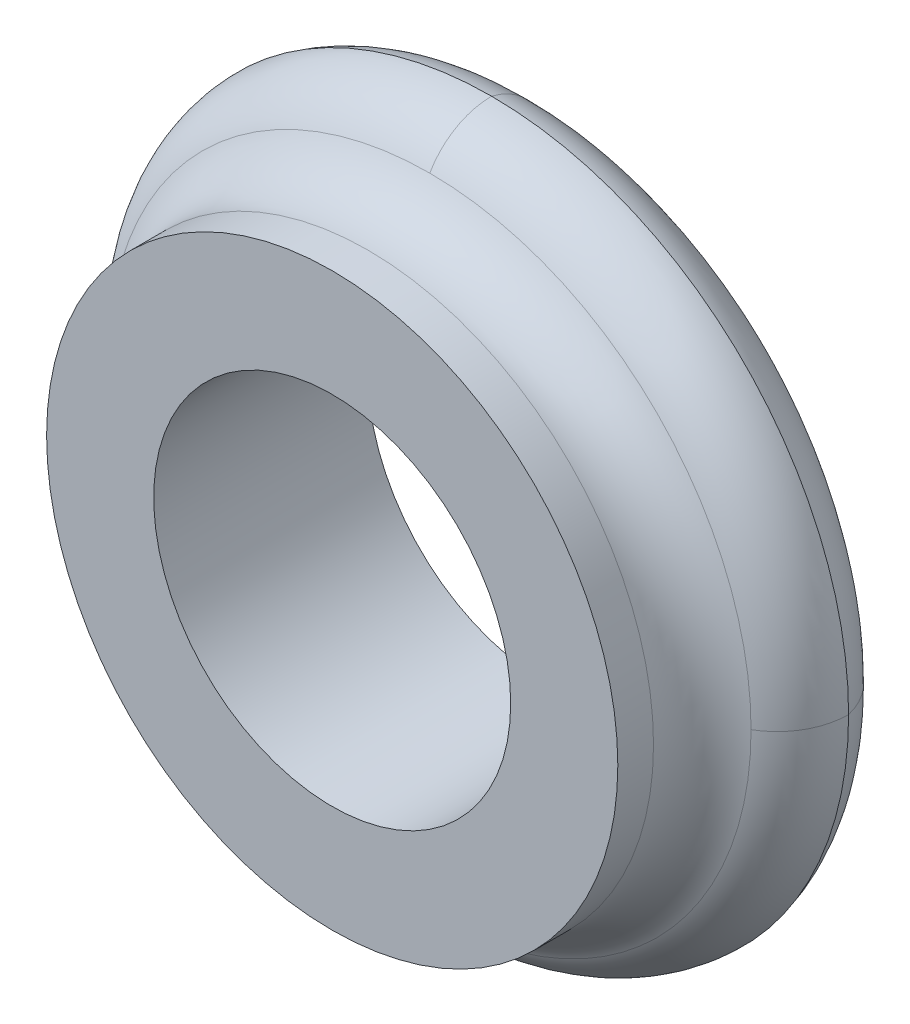
SolidWorks part; units mm, degrees
ref_plane "Alzado" through (0, 0, 0) normal (0, 0, 1) x (1, 0, 0)
ref_plane "Planta" through (0, 0, 0) normal (0, 1, 0) x (1, 0, 0)
ref_plane "Vista lateral" through (0, 0, 0) normal (1, 0, 0) x (0, 0, -1)
sketch "Croquis1" plane through (0, 0, 0) normal (0, 0, 1) x (1, 0, 0)
sketch "Croquis4" plane through (0, 0, 0) normal (0, 0, 1) x (1, 0, 0)
  line L1 (-5, -5) -> (5, -5)
  line L2 (-5, -5) -> (-5, 5)
  line L3 (-5, 5) -> (5, 5)
  line L4 (5, -5) -> (5, 5)
  line L5 (-5, -5) -> (5, 5) construction
  line L6 (-5, 5) -> (5, -5) construction
  circle A0 centre (0, 0) radius 4
  circle A1 centre (0, 0) radius 2.5
  dimension "D1" = 8
  dimension "D2" = 5
  dimension "D3" = 10
  dimension "D4" = 10
extrude "Saliente-Extruir3" add sketch "Croquis4" along normal blind 3 contours A0 A1 region at (-3.8869, 0, 0)
extrude "Saliente-Extruir4" add sketch "Croquis4<4>" along normal blind 1.5 contours L1 L4 L3 L2 A0 region at (-4.8586, 0, 0)
sketch "Croquis4<4>" plane through (0, 0, 0) normal (0, 0, 1) x (1, 0, 0) same geometry as "Croquis4"
fillet "Redondeo6" radius 5 4 edges at (-5, 5, 0.75) (5, 5, 0.75) (5, -5, 0.75) (-5, -5, 0.75)
fillet "Redondeo8" radius 1 1 edges at (4, 0, 1.5)
fillet "Redondeo9" radius 1 4 edges at (3.5355, -3.5355, 1.5) (-3.5355, -3.5355, 1.5) (-3.5355, 3.5355, 1.5) (3.5355, 3.5355, 1.5)
fillet "Redondeo10" radius 1 4 edges at (3.5355, -3.5355, 0) (3.5355, 3.5355, 0) (-3.5355, 3.5355, 0) (-3.5355, -3.5355, 0)
